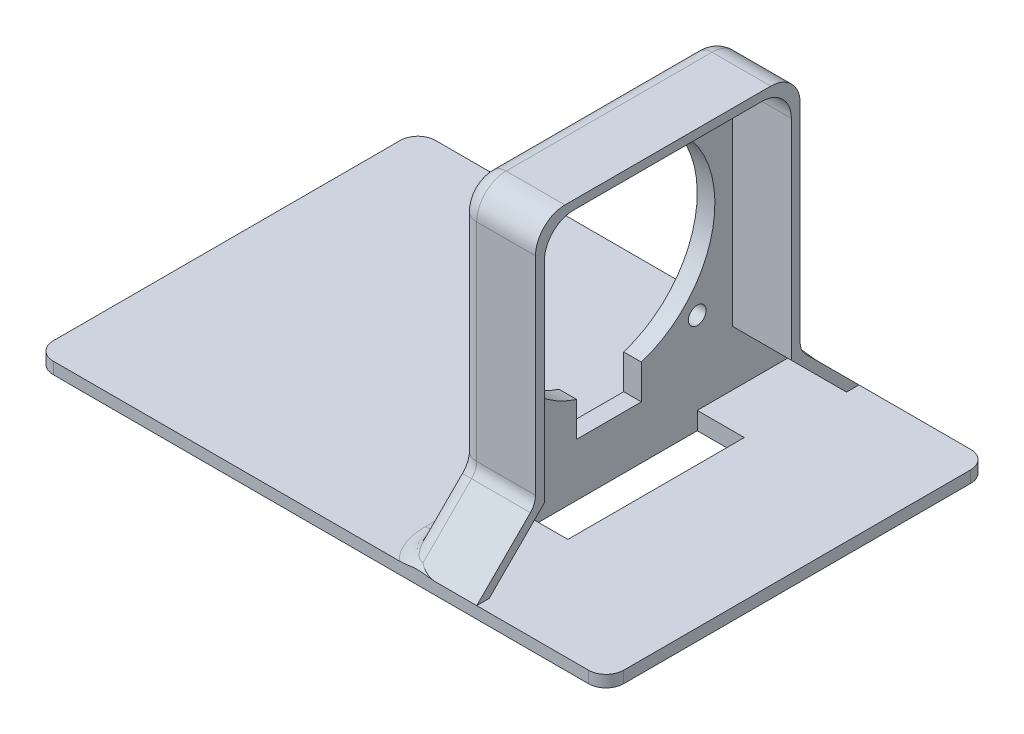
SolidWorks part; units mm, degrees
ref_plane "Front Plane" through (0, 0, 0) normal (0, 0, 1) x (1, 0, 0)
ref_plane "Top Plane" through (0, 0, 0) normal (0, 1, 0) x (1, 0, 0)
ref_plane "Right Plane" through (0, 0, 0) normal (1, 0, 0) x (0, 0, -1)
sketch "Sketch1" plane through (0, 0, 0) normal (0, 1, 0) x (1, 0, 0)
  line L1 (-48.5, 32.5) -> (48.5, 32.5)
  line L2 (-48.5, 32.5) -> (-48.5, -32.5)
  line L3 (-48.5, -32.5) -> (48.5, -32.5)
  line L4 (48.5, 32.5) -> (48.5, -32.5)
  line L5 (-48.5, 32.5) -> (48.5, -32.5) construction
  line L6 (-48.5, -32.5) -> (48.5, 32.5) construction
  point P0 (0, 0)
  dimension "D1" = 97
  dimension "D2" = 65
extrude "Boss-Extrude1" add sketch "Sketch1" along normal blind 2
fillet "Fillet1" radius 3 4 edges at (48.5, 1, -32.5) (48.5, 1, 32.5) (-48.5, 1, 32.5) (-48.5, 1, -32.5)
sketch "Sketch2" plane through (0, 0, 0) normal (0, -1, 0) x (1, 0, 0)
  line L4 (-48.5, -29.5) -> (-48.5, 29.5) construction
  line L5 (-46.4, -30.4) -> (46.4, -30.4)
  line L6 (-46.4, -30.4) -> (-46.4, 30.4)
  line L7 (-46.4, 30.4) -> (46.4, 30.4)
  line L8 (46.4, -30.4) -> (46.4, 30.4)
  line L9 (-46.4, -30.4) -> (46.4, 30.4) construction
  line L10 (-46.4, 30.4) -> (46.4, -30.4) construction
  line L11 (-45.5, 32.5) -> (45.5, 32.5) construction
  point P0 (0, 0)
  point P6 (0, 0)
  point P7 (0, 0)
  point P8 (0, 0)
  dimension "D1" = 2.1
  dimension "D2" = 2.1
extrude "Boss-Extrude2" add sketch "Sketch2" along normal blind 1
fillet "Fillet2" radius 3 4 edges at (46.4, -0.5, 30.4) (46.4, -0.5, -30.4) (-46.4, -0.5, -30.4) (-46.4, -0.5, 30.4)
ref_plane "Plane1" through (16.5, 0, 0) normal (1, 0, 0) x (0, 0, -1)
sketch "Sketch3" plane through (16.5, 0, 0) normal (1, 0, 0) x (0, 0, -1)
  line L0 (0, 0) -> (0, 43.8719) construction
  line L1 (-29.5, 2) -> (29.5, 2) construction
  line L2 (-32.5, 2) -> (-22.5, 12)
  line L4 (-22.5, 12) -> (-22.5, 53.5)
  line L5 (-22.5, 53.5) -> (22.5, 53.5)
  line L6 (22.5, 12) -> (22.5, 53.5)
  line L7 (-22.5, 8.5) -> (22.5, 53.5) construction
  line L8 (-22.5, 53.5) -> (22.5, 8.5) construction
  line L9 (32.5, 2) -> (22.5, 12)
  line L10 (-32.5, 2) -> (32.5, 2)
  circle A0 centre (0, 31) radius 18 construction
  dimension "D1" = 36
  dimension "D2" = 29
  dimension "D3" = 45
  dimension "D4" = 45
extrude "Boss-Extrude3" add sketch "Sketch3" against normal blind 3
sketch "Sketch4" plane through (16.5, 0, 0) normal (1, 0, 0) x (0, 0, -1)
  line L0 (0, 53.5) -> (0, 0) construction
  line L1 (22.5, 53.5) -> (-22.5, 53.5) construction
  line L2 (-29.5, 2) -> (29.5, 2) construction
  circle A0 centre (0, 31) radius 18
  dimension "D1" = 36
  dimension "D2" = 29
extrude "Cut-Extrude1" cut sketch "Sketch4" against normal up to next
sketch "Sketch5" plane through (16.5, 0, 0) normal (1, 0, 0) x (0, 0, -1)
  line L0 (0, 0) -> (0, 13) construction
  line L2 (-5.5, 8) -> (5.5, 8)
  line L3 (-5.5, 8) -> (-5.5, 18)
  line L4 (-5.5, 18) -> (5.5, 18)
  line L5 (5.5, 8) -> (5.5, 18)
  line L6 (-5.5, 8) -> (5.5, 18) construction
  line L7 (-5.5, 18) -> (5.5, 8) construction
  circle A0 centre (0, 31) radius 18 construction
  dimension "D1" = 11
  dimension "D2" = 10
extrude "Cut-Extrude2" cut sketch "Sketch5" against normal up to next
sketch "Sketch6" plane through (16.5, 0, 0) normal (1, 0, 0) x (0, 0, -1)
  line L0 (-22.5, 53.5) -> (-22.5, 12) construction
  line L1 (22.5, 53.5) -> (-22.5, 53.5) construction
  line L2 (22.5, 12) -> (22.5, 53.5) construction
  line L3 (32.5, 2) -> (22.5, 12) construction
  line L4 (-32.5, 2) -> (32.5, 2) construction
  line L5 (-22.5, 12) -> (-32.5, 2) construction
  line L6 (-22.5, 53.5) -> (-22.5, 12)
  line L7 (22.5, 53.5) -> (-22.5, 53.5)
  line L8 (22.5, 12) -> (22.5, 53.5)
  line L9 (32.5, 2) -> (22.5, 12)
  line L10 (-32.5, 2) -> (-30.3787, 2)
  line L11 (-22.5, 12) -> (-32.5, 2)
  line L12 (30.3787, 2) -> (21, 11.3787)
  line L13 (21, 11.3787) -> (21, 52)
  line L14 (21, 52) -> (-21, 52)
  line L15 (-21, 52) -> (-21, 11.3787)
  line L16 (-21, 11.3787) -> (-30.3787, 2)
  line L17 (-32.5, 2) -> (-30.3787, 2)
  line L18 (30.3787, 2) -> (32.5, 2)
  line L19 (30.3787, 2) -> (32.5, 2)
  line L20 (31.4393, 0.9393) -> (21, 11.3787) construction
  line L21 (-21, 11.3787) -> (-31.4393, 0.9393) construction
  line M11 (22.5, 12) -> (22.5, 53.5)
  line M12 (22.5, 53.5) -> (-22.5, 53.5)
  line M13 (-22.5, 53.5) -> (-22.5, 12)
  line M14 (-22.5, 12) -> (-32.5, 2)
  line M15 (-32.5, 2) -> (32.5, 2)
  line M16 (32.5, 2) -> (22.5, 12)
  dimension "D1" = 1.5
extrude "Boss-Extrude4" add sketch "Sketch6" along normal blind 10 contours L16 L15 L14 L13 L12 M15 M16 M11 M12 M13 M14 region at (16.5, 52.6707, 0)
sketch "Sketch8" plane through (16.5, 0, 0) normal (1, 0, 0) x (0, 0, -1)
  line L0 (0, 52) -> (0, 0) construction
  line L1 (21, 52) -> (-21, 52) construction
  line L2 (-18, 31) -> (18, 31) construction
  arc A0 (5.5, 13.8609) -> (-5.5, 13.8609) centre (0, 31) ccw construction
  circle A1 centre (-15, 46) radius 1.5
  circle A2 centre (15, 46) radius 1.5
  circle A3 centre (15, 16) radius 1.5
  circle A4 centre (-15, 16) radius 1.5
  dimension "D1" = 3
  dimension "D2" = 30
  dimension "D3" = 30
extrude "Cut-Extrude3" cut sketch "Sketch8" against normal up to next
sketch "Sketch9" plane through (0, 2, 0) normal (0, 1, 0) x (1, 0, 0)
  line L0 (13.5, 0) -> (48.5, 0) construction
  line L1 (13.5, -32.5) -> (13.5, 32.5) construction
  line L2 (48.5, -29.5) -> (48.5, 29.5) construction
  line L3 (16.5, 15) -> (24.5, 15)
  line L4 (16.5, -29.7968) -> (16.5, 29.7968) construction
  line L5 (24.5, 15) -> (24.5, -15)
  line L6 (16.5, 15) -> (16.5, -15)
  line L7 (16.5, -15) -> (24.5, -15)
  point P13 (24.5, 0)
  point P14 (16.5, 0)
  dimension "D1" = 30
  dimension "D2" = 8
extrude "Cut-Extrude4" cut sketch "Sketch9" against normal through all
fillet "Fillet3" radius 3 7 edges at (20, 12, 22.5) (20, 12, -22.5) (13.5, 32.75, -22.5) (13.5, 7, -27.5) (13.5, 7, 27.5) (13.5, 32.75, 22.5) (13.5, 53.5, 0)
fillet "Fillet4" radius 3 3 edges at (14.3787, 2, 31.2574) (14.3787, 2, -31.2574) (13.5, 2, 0)
fillet "Fillet6" radius 5 2 edges at (21.5, 52, -21) (21.5, 52, 21)
fillet "Fillet7" radius 5 4 edges at (14.3787, 52.6213, 21.6213) (14.3787, 52.6213, -21.6213) (21.5, 53.5, -22.5) (21.5, 53.5, 22.5)
